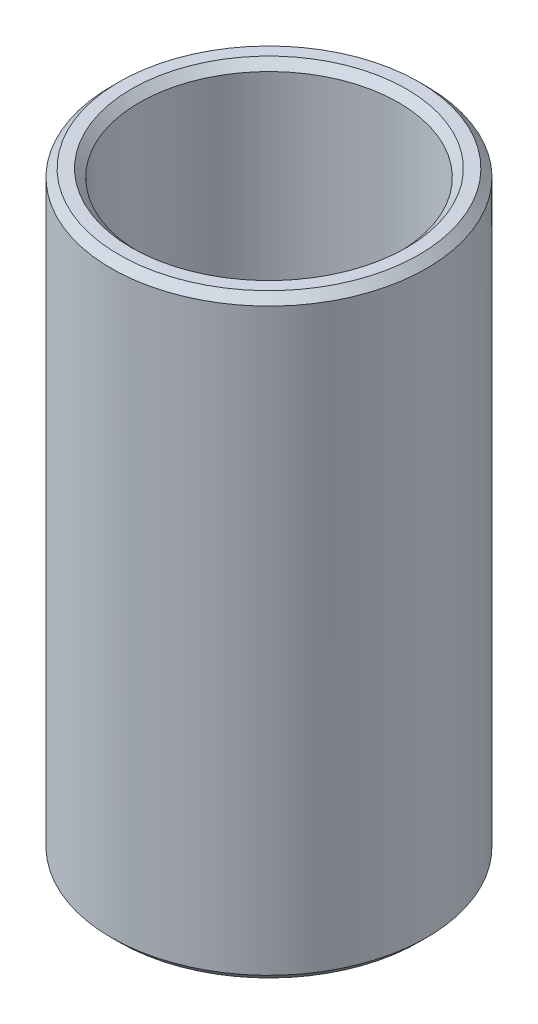
SolidWorks part; units mm, degrees
ref_plane "Front Plane" through (0, 0, 0) normal (0, 0, 1) x (1, 0, 0)
ref_plane "Top Plane" through (0, 0, 0) normal (0, 1, 0) x (1, 0, 0)
ref_plane "Right Plane" through (0, 0, 0) normal (1, 0, 0) x (0, 0, -1)
sketch "Sketch1" plane through (0, 0, 0) normal (0, 1, 0) x (1, 0, 0)
  circle A0 centre (0, 0) radius 52.5
  dimension "SLEEVE_OD" = 105
extrude "Boss-Extrude1" add sketch "Sketch1" along normal blind 198.1737
sketch "Sketch2" plane through (0, 0, 0) normal (0, 1, 0) x (1, 0, 0)
  circle A0 centre (0, 0) radius 43.1692
  dimension "BORE_D" = 86.3385
extrude "Cut-Extrude1" cut sketch "Sketch2" along normal through all
chamfer "Chamfer1" distance 2.6121 angle 45 4 edges at (0, 198.1737, 43.1692) (0, 0, 43.1692) (0, 0, 52.5) (0, 198.1737, 52.5)
